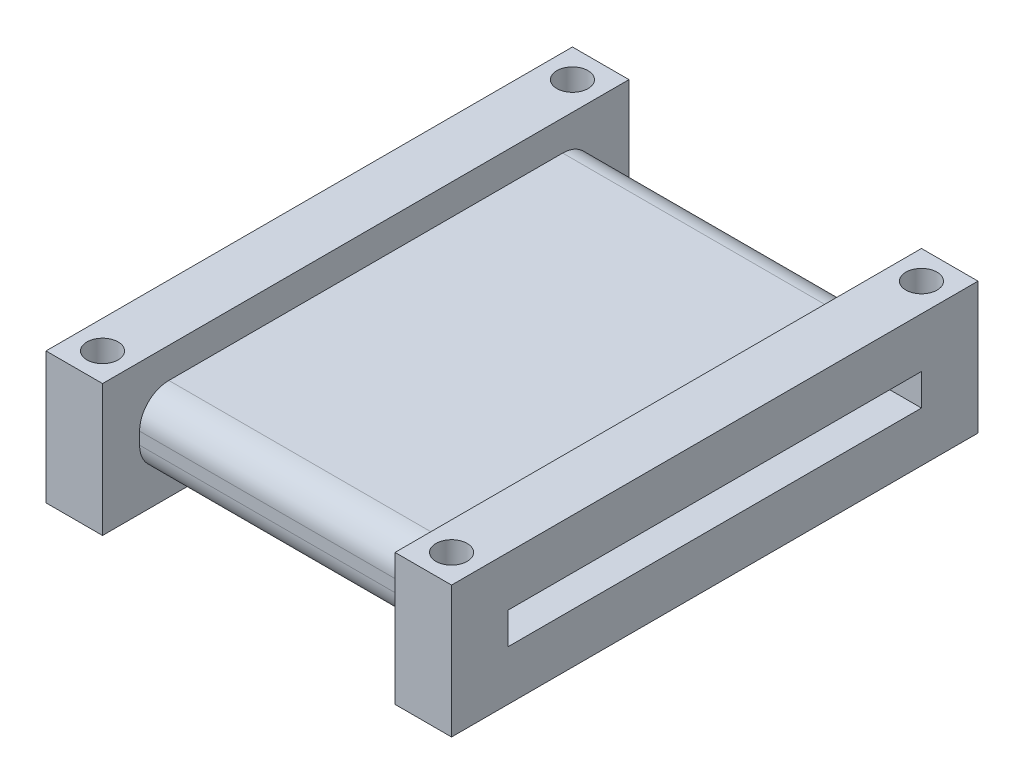
SolidWorks part; units mm, degrees
ref_plane "Front Plane" through (0, 0, 0) normal (0, 0, 1) x (1, 0, 0)
ref_plane "Top Plane" through (0, 0, 0) normal (0, 1, 0) x (1, 0, 0)
ref_plane "Right Plane" through (0, 0, 0) normal (1, 0, 0) x (0, 0, -1)
sketch "Sketch1" plane through (0, 0, 0) normal (1, 0, 0) x (0, 0, -1)
  line L0 (23.2, 7.25) -> (23.2, 0) construction
  line L1 (0, 0) -> (46.4, 0)
  line L2 (0, 0) -> (0, 7.25)
  line L3 (0, 7.25) -> (46.4, 7.25)
  line L4 (46.4, 0) -> (46.4, 7.25)
  line L6 (2, 2) -> (44.4, 2)
  line L7 (2, 2) -> (2, 5.25)
  line L8 (2, 5.25) -> (44.4, 5.25)
  line L9 (44.4, 2) -> (44.4, 5.25)
  line L10 (2, 2) -> (44.4, 5.25) construction
  line L11 (2, 5.25) -> (44.4, 2) construction
  point P7 (23.2, 3.625)
  dimension "D1" = 46.4
  dimension "D2" = 7.25
  dimension "D3" = 3.25
  dimension "D4" = 42.4
extrude "Boss-Extrude1" add sketch "Sketch1" along normal blind 30
fillet "Fillet2" radius 3 4 edges at (15, 0, -46.4) (15, 0, 0) (15, 7.25, 0) (15, 7.25, -46.4)
sketch "Sketch2" plane through (30, 0, 0) normal (1, 0, 0) x (0, 0, -1)
  line L0 (23.2, 7.25) -> (23.2, 0) construction
  line L1 (43.4, 7.25) -> (3, 7.25) construction
  line L2 (3, 0) -> (43.4, 0) construction
  line L4 (-3.8, -3.125) -> (50.2, -3.125)
  line L5 (-3.8, -3.125) -> (-3.8, 10.375)
  line L6 (-3.8, 10.375) -> (50.2, 10.375)
  line L7 (50.2, -3.125) -> (50.2, 10.375)
  line L8 (-3.8, -3.125) -> (50.2, 10.375) construction
  line L9 (-3.8, 10.375) -> (50.2, -3.125) construction
  line L14 (44.4, 2) -> (2, 2)
  line L15 (44.4, 2) -> (44.4, 5.25)
  line L16 (44.4, 5.25) -> (2, 5.25)
  line L17 (2, 2) -> (2, 5.25)
  line L18 (44.4, 2) -> (2, 5.25) construction
  line L19 (44.4, 5.25) -> (2, 2) construction
  point P6 (23.2, 3.625)
  point P11 (23.2, 3.625)
  point P12 (23.2, 3.625)
  dimension "D1" = 13.5
  dimension "D2" = 54
extrude "Boss-Extrude2" add sketch "Sketch2" along normal blind 5.8
sketch "Sketch3" plane through (0, 0, 0) normal (-1, 0, 0) x (0, 0, 1)
  line L0 (-23.2, 7.25) -> (-23.2, 0) construction
  line L1 (-43.4, 7.25) -> (-3, 7.25) construction
  line L2 (-3, 0) -> (-43.4, 0) construction
  line L4 (3.8, -3.125) -> (-50.2, -3.125)
  line L5 (3.8, -3.125) -> (3.8, 10.375)
  line L6 (3.8, 10.375) -> (-50.2, 10.375)
  line L7 (-50.2, -3.125) -> (-50.2, 10.375)
  line L8 (3.8, -3.125) -> (-50.2, 10.375) construction
  line L9 (3.8, 10.375) -> (-50.2, -3.125) construction
  line L10 (-2, 2) -> (-44.4, 2)
  line L11 (-2, 2) -> (-2, 5.25)
  line L12 (-2, 5.25) -> (-44.4, 5.25)
  line L13 (-44.4, 2) -> (-44.4, 5.25)
  line L14 (-2, 2) -> (-44.4, 5.25) construction
  line L15 (-2, 5.25) -> (-44.4, 2) construction
  point P6 (-23.2, 3.625)
  point P12 (-23.2, 3.625)
extrude "Boss-Extrude3" add sketch "Sketch3" along normal blind 5.8
sketch "Sketch4" plane through (0, 10.375, 0) normal (0, 1, 0) x (1, 0, 0)
  line L0 (-2.9, 50.2) -> (-2.9, 47.3) construction
  line L1 (-5.8, 50.2) -> (0, 50.2) construction
  line L2 (32.9, 50.2) -> (32.9, 47.3) construction
  line L3 (35.8, 50.2) -> (30, 50.2) construction
  line L4 (-2.9, -3.8) -> (-2.9, -0.9) construction
  line L5 (-5.8, -3.8) -> (0, -3.8) construction
  line L6 (32.9, -3.8) -> (32.9, -0.9) construction
  line L7 (35.8, -3.8) -> (30, -3.8) construction
  circle A0 centre (-2.9, 47.3) radius 1.6
  circle A1 centre (32.9, 47.3) radius 1.6
  circle A2 centre (-2.9, -0.9) radius 1.6
  circle A3 centre (32.9, -0.9) radius 1.6
  dimension "D2" = 3.2
  dimension "D4" = 3.2
  dimension "D6" = 3.2
  dimension "D8" = 3.2
  dimension "D1" = 2.9
  dimension "D3" = 2.9
  dimension "D5" = 2.9
  dimension "D7" = 2.9
extrude "Cut-Extrude1" cut sketch "Sketch4" against normal through all
sketch "Sketch6" plane through (35.8, 0, 0) normal (1, 0, 0) x (0, 0, -1)
  line L0 (50.2, -3.125) -> (50.2, 10.375) construction
  line L1 (-3.8, -3.125) -> (50.2, -3.125)
  line L2 (-3.8, -3.125) -> (-3.8, 4.075)
  line L3 (-3.8, 4.075) -> (50.2, 4.075)
  line L4 (50.2, -3.125) -> (50.2, 4.075)
  dimension "D1" = 7.2
extrude "Cut-Extrude2" [suppressed] cut sketch "Sketch6" against normal blind 5.8
sketch "Sketch7" plane through (-5.8, 0, 0) normal (-1, 0, 0) x (0, 0, 1)
  line L0 (3.8, -3.125) -> (3.8, 10.375) construction
  line L1 (-50.2, -3.125) -> (3.8, -3.125)
  line L2 (-50.2, -3.125) -> (-50.2, 4.075)
  line L3 (-50.2, 4.075) -> (3.8, 4.075)
  line L4 (3.8, -3.125) -> (3.8, 4.075)
  dimension "D1" = 7.2
extrude "Cut-Extrude3" [suppressed] cut sketch "Sketch7" against normal blind 5.8
